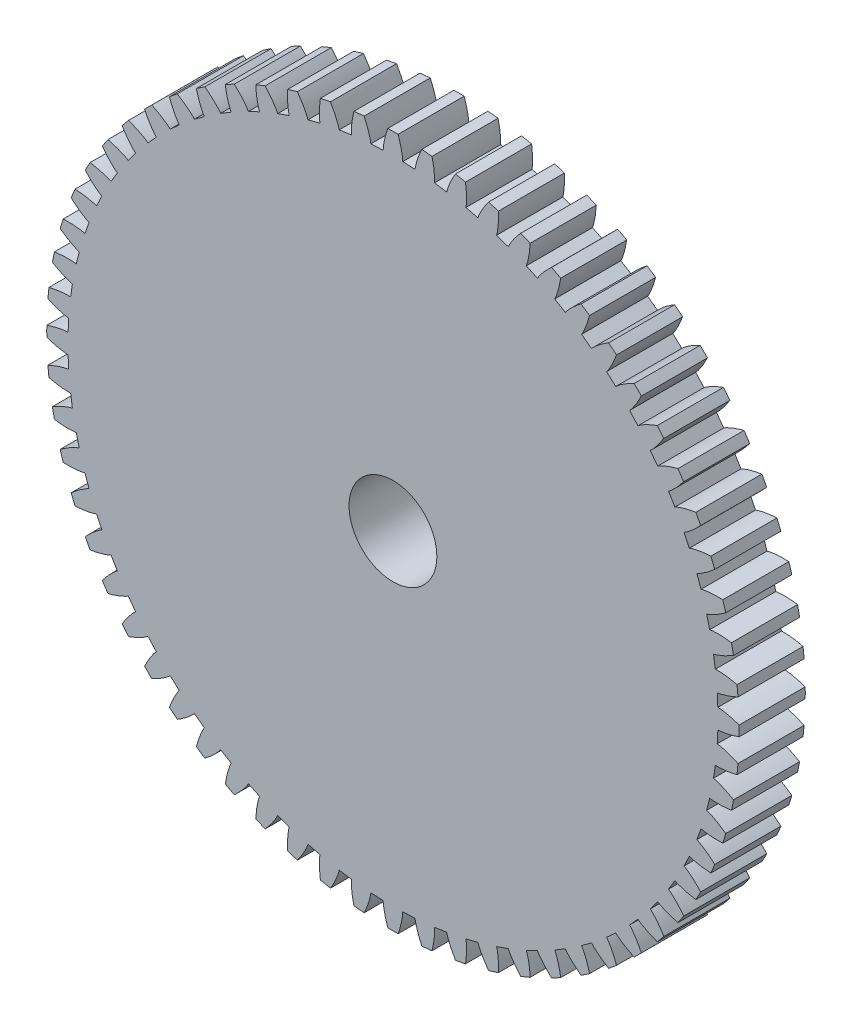
SolidWorks part; units mm, degrees
material "Plain Carbon Steel"
ref_plane "Front Plane" through (0, 0, 0) normal (0, 0, 1) x (1, 0, 0)
ref_plane "Top Plane" through (0, 0, 0) normal (0, 1, 0) x (1, 0, 0)
ref_plane "Right Plane" through (0, 0, 0) normal (1, 0, 0) x (0, 0, -1)
sketch "Sketch1" plane through (0, 0, 0) normal (0, 0, 1) x (1, 0, 0)
  circle A0 centre (0, 0) radius 52.3875
  dimension "D1" = 104.775
extrude "Boss-Extrude1" add sketch "Sketch1" along normal blind 10
sketch "Sketch2" plane through (0, 0, 0) normal (0, 0, 1) x (1, 0, 0)
  spline S0 degree 4 poles (49.1596, 1.4796) (49.1645, 1.4797) (49.1783, 1.4799) (49.2042, 1.4798) (49.2467, 1.4789) (49.3008, 1.4769) (49.3708, 1.4732) (49.4534, 1.4673) (49.5443, 1.4594) (49.6433, 1.4491) (49.7422, 1.4374) (49.841, 1.4244) (49.9396, 1.4103) (50.0592, 1.3917) (50.2028, 1.3674) (50.371, 1.3361) (50.5622, 1.2971) (50.7575, 1.2536) (50.9501, 1.2078) (51.1452, 1.158) (51.3344, 1.1072) (51.5315, 1.0509) (51.7136, 0.9971) (51.9184, 0.9327) (52.0839, 0.8796) (52.3029, 0.8051) (52.4325, 0.7599) (52.5844, 0.7054) (52.652, 0.6804) (52.6936, 0.6651) knots 0 0 0 0 0 0.005377 0.015084 0.028532 0.04661 0.064855 0.092111 0.119476 0.146842 0.174209 0.201575 0.228941 0.256307 0.307035 0.361767 0.4165 0.471232 0.525964 0.580697 0.635429 0.690161 0.744894 0.799626 0.854358 0.909091 0.954545 1 1 1 1 1 construction
  spline S1 degree 4 poles (49.1596, 1.4796) (49.1645, 1.4797) (49.1783, 1.4799) (49.2042, 1.4798) (49.2467, 1.4789) (49.3008, 1.4769) (49.3708, 1.4732) (49.4534, 1.4673) (49.5443, 1.4594) (49.6433, 1.4491) (49.7422, 1.4374) (49.841, 1.4244) (49.9396, 1.4103) (50.0592, 1.3917) (50.2028, 1.3674) (50.371, 1.3361) (50.5622, 1.2971) (50.7575, 1.2536) (50.9501, 1.2078) (51.1452, 1.158) (51.3344, 1.1072) (51.5315, 1.0509) (51.7136, 0.9971) (51.9184, 0.9327) (52.0839, 0.8796) (52.2554, 0.8213) (52.339, 0.7924) (52.3817, 0.7774) knots 0 0 0 0 0 0.005377 0.015084 0.028532 0.04661 0.064855 0.092111 0.119476 0.146842 0.174209 0.201575 0.228941 0.256307 0.307035 0.361767 0.4165 0.471232 0.525964 0.580697 0.635429 0.690161 0.744894 0.799626 0.854358 0.909091 0.909091 0.909091 0.909091 0.909091
  spline S2 degree 4 poles (49.0679, 3.346) (49.0728, 3.3464) (49.0865, 3.3476) (49.1123, 3.3502) (49.1545, 3.3552) (49.2081, 3.3625) (49.2774, 3.3731) (49.3591, 3.387) (49.4487, 3.4038) (49.5463, 3.4238) (49.6436, 3.4451) (49.7407, 3.4677) (49.8374, 3.4915) (49.9546, 3.5217) (50.0951, 3.5599) (50.2594, 3.6076) (50.4458, 3.6651) (50.6359, 3.7275) (50.8232, 3.792) (51.0125, 3.8607) (51.1957, 3.9297) (51.3863, 4.0051) (51.5624, 4.0765) (51.7599, 4.1607) (51.9193, 4.2298) (52.13, 4.3253) (52.2545, 4.3831) (52.4003, 4.4522) (52.4652, 4.4836) (52.5051, 4.503) knots 0 0 0 0 0 0.005377 0.015084 0.028532 0.04661 0.064855 0.092111 0.119476 0.146842 0.174209 0.201575 0.228941 0.256307 0.307035 0.361767 0.4165 0.471232 0.525964 0.580697 0.635429 0.690161 0.744894 0.799626 0.854358 0.909091 0.954545 1 1 1 1 1 construction
  spline S3 degree 4 poles (49.0679, 3.346) (49.0728, 3.3464) (49.0865, 3.3476) (49.1123, 3.3502) (49.1545, 3.3552) (49.2081, 3.3625) (49.2774, 3.3731) (49.3591, 3.387) (49.4487, 3.4038) (49.5463, 3.4238) (49.6436, 3.4451) (49.7407, 3.4677) (49.8374, 3.4915) (49.9546, 3.5217) (50.0951, 3.5599) (50.2594, 3.6076) (50.4458, 3.6651) (50.6359, 3.7275) (50.8232, 3.792) (51.0125, 3.8607) (51.1957, 3.9297) (51.3863, 4.0051) (51.5624, 4.0765) (51.7599, 4.1607) (51.9193, 4.2298) (52.0843, 4.3046) (52.1646, 4.3415) (52.2057, 4.3606) knots 0 0 0 0 0 0.005377 0.015084 0.028532 0.04661 0.064855 0.092111 0.119476 0.146842 0.174209 0.201575 0.228941 0.256307 0.307035 0.361767 0.4165 0.471232 0.525964 0.580697 0.635429 0.690161 0.744894 0.799626 0.854358 0.909091 0.909091 0.909091 0.909091 0.909091
  spline S4 degree 1 poles (49.0679, 3.346) (49.1596, 1.4796) knots 0 0 1 1 construction
  spline S5 degree 1 poles (49.0679, 3.346) (49.1596, 1.4796) knots 0 0 1 1
  spline S6 degree 1 poles (52.3817, 0.7774) (59.9934, 0.8904) knots 0 0 1 1 construction
  spline S7 degree 1 poles (52.3817, 0.7774) (59.9934, 0.8904) knots 0 0 1 1
  spline S8 degree 4 poles (59.9981, 0.4767) (59.9979, 0.5063) (59.9973, 0.5633) (59.9967, 0.6404) (59.9941, 0.8495) (59.9927, 0.941) (59.9881, 1.2106) (59.9845, 1.3636) (59.9793, 1.5848) (59.9741, 1.765) (59.9679, 1.9699) (59.9612, 2.1599) (59.9538, 2.3588) (59.9458, 2.5524) (59.9372, 2.7489) (59.9278, 2.9441) (59.918, 3.1392) (59.9073, 3.3356) (59.8963, 3.5291) (59.8842, 3.7277) (59.8722, 3.9174) (59.8583, 4.122) (59.8458, 4.3018) (59.8293, 4.5225) (59.8179, 4.6751) (59.7961, 4.9439) (59.7884, 5.0351) (59.7706, 5.2434) (59.7637, 5.3202) (59.7586, 5.377) (59.7559, 5.4064) knots 0 0 0 0 0 0.020959 0.041918 0.083333 0.123016 0.162698 0.202381 0.242063 0.281746 0.321429 0.361111 0.400794 0.440476 0.480159 0.519841 0.559524 0.599206 0.638889 0.678571 0.718254 0.757937 0.797619 0.837302 0.876984 0.916667 0.958082 0.979041 1 1 1 1 1 construction
  spline S9 degree 4 poles (59.9934, 0.8904) (59.9928, 0.9312) (59.9915, 1.0106) (59.9881, 1.2106) (59.9845, 1.3636) (59.9793, 1.5848) (59.9741, 1.765) (59.9679, 1.9699) (59.9612, 2.1599) (59.9538, 2.3588) (59.9458, 2.5524) (59.9372, 2.7489) (59.9278, 2.9441) (59.918, 3.1392) (59.9073, 3.3356) (59.8963, 3.5291) (59.8842, 3.7277) (59.8722, 3.9174) (59.8583, 4.122) (59.8458, 4.3018) (59.8293, 4.5225) (59.8179, 4.6751) (59.8017, 4.8745) (59.7952, 4.9536) (59.7918, 4.9943) knots 0.083333 0.083333 0.083333 0.083333 0.083333 0.123016 0.162698 0.202381 0.242063 0.281746 0.321429 0.361111 0.400794 0.440476 0.480159 0.519841 0.559524 0.599206 0.638889 0.678571 0.718254 0.757937 0.797619 0.837302 0.876984 0.916667 0.916667 0.916667 0.916667 0.916667
  spline S10 degree 1 poles (59.7918, 4.9943) (52.2057, 4.3606) knots 0 0 1 1 construction
  spline S11 degree 1 poles (59.7918, 4.9943) (52.2057, 4.3606) knots 0 0 1 1
extrude "Cut-Extrude2" cut sketch "Sketch2" against normal blind 11 and the other way blind 11
ref_axis "Axis1" through (0, 0, -0.5) along (0, 0, 1)
pattern_circular "CirPattern1" count 64 over 360 about axis through (0, 0, -0.5) along (0, 0, 1) of "Cut-Extrude2"
sketch "Sketch3" plane through (0, 0, 0) normal (0, 0, 1) x (1, 0, 0)
  circle A0 centre (0, 0) radius 6.6421
  dimension "D1" = 13.2842
extrude "Cut-Extrude4" cut sketch "Sketch3" against normal blind 12 and the other way blind 12
